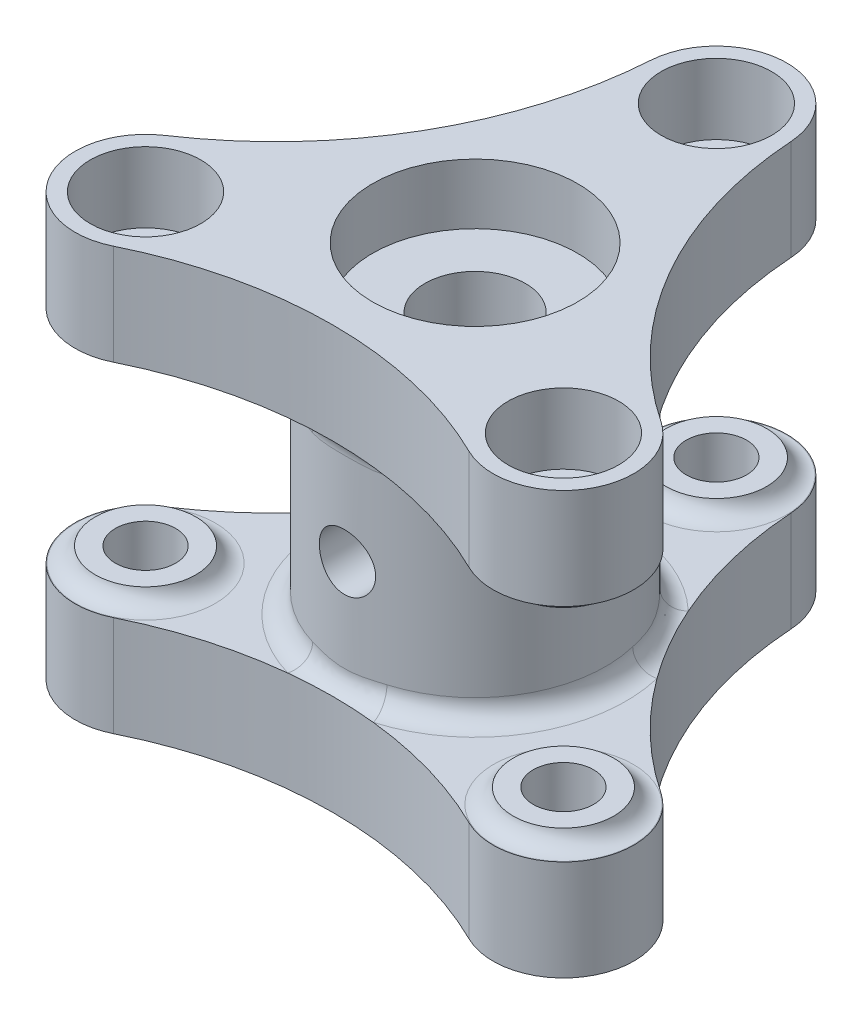
SolidWorks part; units mm, degrees
ref_plane "Front Plane" through (0, 0, 0) normal (0, 0, 1) x (1, 0, 0)
ref_plane "Top Plane" through (0, 0, 0) normal (0, 1, 0) x (1, 0, 0)
ref_plane "Right Plane" through (0, 0, 0) normal (1, 0, 0) x (0, 0, -1)
sketch "Sketch1" plane through (0, 0, 0) normal (0, 1, 0) x (1, 0, 0)
  line L5 (-10.3923, -6) -> (10.3923, -6) construction
  line L9 (-10.3923, -6) -> (0, 12) construction
  line L10 (-1.4309, -2.05) -> (1.4309, -2.05)
  line L11 (0, 12) -> (10.3923, -6) construction
  circle A0 centre (0, 0) radius 15.75 construction
  arc A1 (1.4309, -2.05) -> (-1.4309, -2.05) centre (0, 0) ccw
  circle A3 centre (0, 12) radius 1.5
  circle A5 centre (10.3923, -6) radius 1.5
  circle A6 centre (-10.3923, -6) radius 1.5
  circle A8 centre (0, 12) radius 5 construction
  arc A24 (-12.337, -3.09) -> (-8.8445, -9.1392) centre (-10.3923, -6) ccw
  circle A25 centre (0, 0) radius 17 construction
  arc A27 (-3.4925, 12.2292) -> (3.4925, 12.2292) centre (0, 12) cw
  arc A28 (-3.4925, 12.2292) -> (-12.337, -3.09) centre (-23.4496, 13.5386) cw
  arc A29 (3.4925, 12.2292) -> (12.337, -3.09) centre (23.4496, 13.5386) ccw
  arc A30 (12.337, -3.09) -> (8.8445, -9.1392) centre (10.3923, -6) cw
  arc A31 (-8.8445, -9.1392) -> (8.8445, -9.1392) centre (0, -27.0772) cw
  circle A32 centre (-10.3923, -6) radius 5 construction
  dimension "D1" = 31.5
  dimension "D2" = 5
  dimension "D3" = 3
  dimension "D4" = 10
  dimension "D5" = 20
  dimension "D6" = 2
  dimension "D7" = 2.05
  dimension "D8" = 34
  dimension "D9" = 10
extrude "Boss-Extrude1" add sketch "Sketch1" along normal blind 5
sketch "Sketch2" plane through (0, 5, 0) normal (0, 1, 0) x (1, 0, 0)
  line L0 (-1.4309, -2.05) -> (1.4309, -2.05) construction
  line L1 (-1.4309, -2.05) -> (1.4309, -2.05)
  circle A0 centre (0, 0) radius 6.5
  circle A2 centre (0, 12) radius 5 construction
  arc A3 (1.4309, -2.05) -> (-1.4309, -2.05) centre (0, 0) ccw construction
  arc A4 (1.4309, -2.05) -> (-1.4309, -2.05) centre (0, 0) ccw
  dimension "D1" = 13
  dimension "D3" = 10
extrude "Boss-Extrude2" add sketch "Sketch2" along normal blind 11
sketch "Sketch3" plane through (0, 16, 0) normal (0, 1, 0) x (1, 0, 0)
  line L0 (-1.4309, -2.05) -> (1.4309, -2.05) construction
  line L1 (-1.4309, -2.05) -> (1.4309, -2.05)
  circle A1 centre (-10.3923, -6) radius 1.5 construction
  circle A14 centre (10.3923, -6) radius 1.5 construction
  circle A17 centre (0, 12) radius 1.5 construction
  circle A18 centre (-10.3923, -6) radius 1.5
  circle A19 centre (10.3923, -6) radius 1.5
  circle A22 centre (0, 12) radius 1.5
  arc A23 (-12.337, -3.09) -> (-3.4925, 12.2292) centre (-23.4496, 13.5386) ccw
  arc A24 (-12.337, -3.09) -> (-3.4925, 12.2292) centre (-23.4496, 13.5386) ccw
  arc A25 (8.8445, -9.1392) -> (-8.8445, -9.1392) centre (0, -27.0772) ccw
  arc A26 (8.8445, -9.1392) -> (-8.8445, -9.1392) centre (0, -27.0772) ccw
  arc A27 (-12.337, -3.09) -> (-8.8445, -9.1392) centre (-10.3923, -6) ccw
  arc A28 (8.8445, -9.1392) -> (12.337, -3.09) centre (10.3923, -6) ccw
  arc A29 (8.8445, -9.1392) -> (12.337, -3.09) centre (10.3923, -6) ccw
  arc A30 (3.4925, 12.2292) -> (12.337, -3.09) centre (23.4496, 13.5386) ccw
  arc A31 (3.4925, 12.2292) -> (12.337, -3.09) centre (23.4496, 13.5386) ccw
  arc A32 (3.4925, 12.2292) -> (-3.4925, 12.2292) centre (0, 12) ccw
  arc A37 (-12.337, -3.09) -> (-8.8445, -9.1392) centre (-10.3923, -6) ccw
  arc A43 (3.4925, 12.2292) -> (-3.4925, 12.2292) centre (0, 12) ccw
  arc A45 (1.4309, -2.05) -> (-1.4309, -2.05) centre (0, 0) ccw construction
  arc A46 (1.4309, -2.05) -> (-1.4309, -2.05) centre (0, 0) ccw
  dimension "D1" = 0
extrude "Boss-Extrude3" add sketch "Sketch3" along normal blind 5
sketch "Sketch4" plane through (0, 0, 0) normal (0, 0, 1) x (1, 0, 0)
  line L0 (0, 0) -> (0, 21) construction
  line L3 (8.8445, 21) -> (-8.8445, 21) construction
  circle A0 centre (0, 10.5) radius 1.4
  dimension "D1" = 2.8
extrude "Cut-Extrude1" cut sketch "Sketch4" along normal through all
fillet "Fillet1" radius 1 2 edges at (0, 16, 6.5) (0, 5, -6.5)
sketch "Sketch6" plane through (0, 0, 0) normal (0, -1, 0) x (1, 0, 0)
  line L0 (-13.1423, 4.4123) -> (-10.3923, 2.8246)
  line L17 (2.75, -13.5877) -> (2.75, -10.4123)
  line L18 (2.75, -10.4123) -> (0, -8.8246)
  line L19 (0, -8.8246) -> (-2.75, -10.4123)
  line L20 (-2.75, -10.4123) -> (-2.75, -13.5877)
  line L21 (-2.75, -13.5877) -> (0, -15.1754)
  line L22 (0, -15.1754) -> (2.75, -13.5877)
  line L23 (-10.3923, 2.8246) -> (-7.6423, 4.4123)
  line L24 (-7.6423, 4.4123) -> (-7.6423, 7.5877)
  line L25 (-7.6423, 7.5877) -> (-10.3923, 9.1754)
  line L26 (-10.3923, 9.1754) -> (-13.1423, 7.5877)
  line L27 (-13.1423, 7.5877) -> (-13.1423, 4.4123)
  line L28 (10.3923, 9.1754) -> (7.6423, 7.5877)
  line L29 (7.6423, 7.5877) -> (7.6423, 4.4123)
  line L30 (7.6423, 4.4123) -> (10.3923, 2.8246)
  line L31 (10.3923, 2.8246) -> (13.1423, 4.4123)
  line L32 (13.1423, 4.4123) -> (13.1423, 7.5877)
  line L33 (13.1423, 7.5877) -> (10.3923, 9.1754)
  circle A0 centre (0, -12) radius 2.75 construction
  circle A1 centre (10.3923, 6) radius 2.75 construction
  circle A2 centre (-10.3923, 6) radius 2.75 construction
  point P45 (0, 0)
  dimension "D1" = 5.5
  dimension "D2" = 3
extrude "Cut-Extrude2" cut sketch "Sketch6" against normal blind 3
sketch "Sketch8" plane through (0, 5, 0) normal (0, 1, 0) x (1, 0, 0)
  circle A0 centre (-10.3923, -6) radius 2.5
  circle A1 centre (-10.3923, -6) radius 1.5 construction
  circle A2 centre (-10.3923, -6) radius 1.5
  circle A3 centre (0, 12) radius 2.5
  circle A4 centre (0, 12) radius 1.5
  circle A5 centre (10.3923, -6) radius 2.5
  circle A6 centre (10.3923, -6) radius 1.5
  circle A12 centre (0, 12) radius 1.5 construction
  point P24 (0, 0)
  dimension "D1" = 5
  dimension "D2" = 3
extrude "Boss-Extrude5" add sketch "Sketch8" along normal blind 0.75
fillet "Fillet4" radius 1 3 edges at (0, 5, -14.5) (10.3923, 5, 3.5) (-10.3923, 5, 3.5)
sketch "Sketch9" plane through (0, 16, 0) normal (0, -1, 0) x (1, 0, 0)
  circle A0 centre (0, -12) radius 2.5
  circle A1 centre (0, -12) radius 1.5 construction
  circle A2 centre (0, -12) radius 1.5
  circle A3 centre (-10.3923, 6) radius 2.5
  circle A4 centre (-10.3923, 6) radius 1.5
  circle A5 centre (10.3923, 6) radius 2.5
  circle A6 centre (10.3923, 6) radius 1.5
  circle A12 centre (-10.3923, 6) radius 1.5 construction
  point P25 (0, 0)
  dimension "D1" = 5
  dimension "D2" = 3
extrude "Boss-Extrude6" add sketch "Sketch9" along normal blind 0.75
fillet "Fillet5" radius 1 3 edges at (10.3923, 16, 8.5) (-10.3923, 16, 8.5) (0, 16, -9.5)
sketch "Sketch12" plane through (0, 21, 0) normal (0, 1, 0) x (1, 0, 0)
  circle A0 centre (0, 12) radius 2.75
  circle A1 centre (10.3923, -6) radius 2.75
  circle A2 centre (-10.3923, -6) radius 2.75
  point P13 (0, 0)
  dimension "D1" = 5.5
  dimension "D2" = 3
extrude "Cut-Extrude5" cut sketch "Sketch12" against normal offset from surface (3.5 mm away) 1.5 up to face at (-10.3923, 16, 9.4682)
sketch "Sketch10" plane through (0, 21, 0) normal (0, 1, 0) x (1, 0, 0)
  circle A0 centre (0, 0) radius 5.1
  dimension "D1" = 10.2
extrude "Cut-Extrude3" cut sketch "Sketch10" against normal blind 3
sketch "Sketch11" plane through (0, 0, 0) normal (0, -1, 0) x (1, 0, 0)
  circle A0 centre (0, 0) radius 5.1
  dimension "D1" = 10.2
extrude "Cut-Extrude4" cut sketch "Sketch11" against normal blind 3.5
